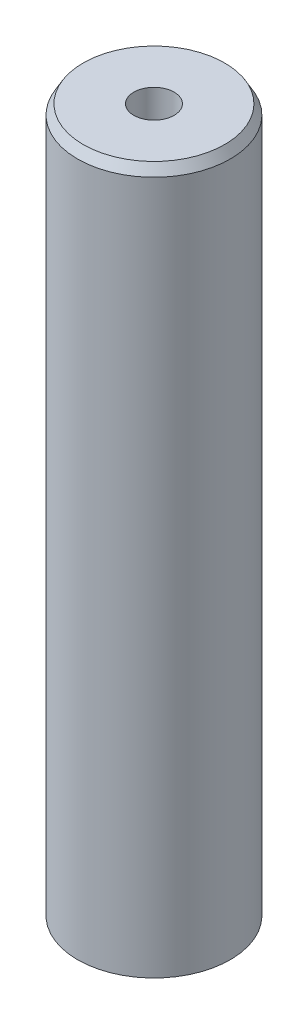
SolidWorks part; units mm, degrees
ref_plane "Front Plane" through (0, 0, 0) normal (0, 0, 1) x (1, 0, 0)
ref_plane "Top Plane" through (0, 0, 0) normal (0, 1, 0) x (1, 0, 0)
ref_plane "Right Plane" through (0, 0, 0) normal (1, 0, 0) x (0, 0, -1)
sketch "Sketch1" plane through (0, 0, 0) normal (0, 1, 0) x (1, 0, 0)
  circle A0 centre (0, 0) radius 7.5
  dimension "SHAFT_OD" = 15
extrude "Boss-Extrude1" add sketch "Sketch1" along normal blind 69.6352
sketch "Sketch2" plane through (0, 0, 0) normal (0, 1, 0) x (1, 0, 0)
  circle A0 centre (0, 0) radius 1.9807
  dimension "BORE_D" = 3.9613
extrude "Cut-Extrude1" cut sketch "Sketch2" along normal through all
chamfer "Chamfer1" distance 0.9558 angle 30 2 edges at (0, 69.6352, 7.5) (0, 0, 7.5) first distance on face at (0, 69.6352, 7.5) first distance on face at (0, 0, 1.9807)
